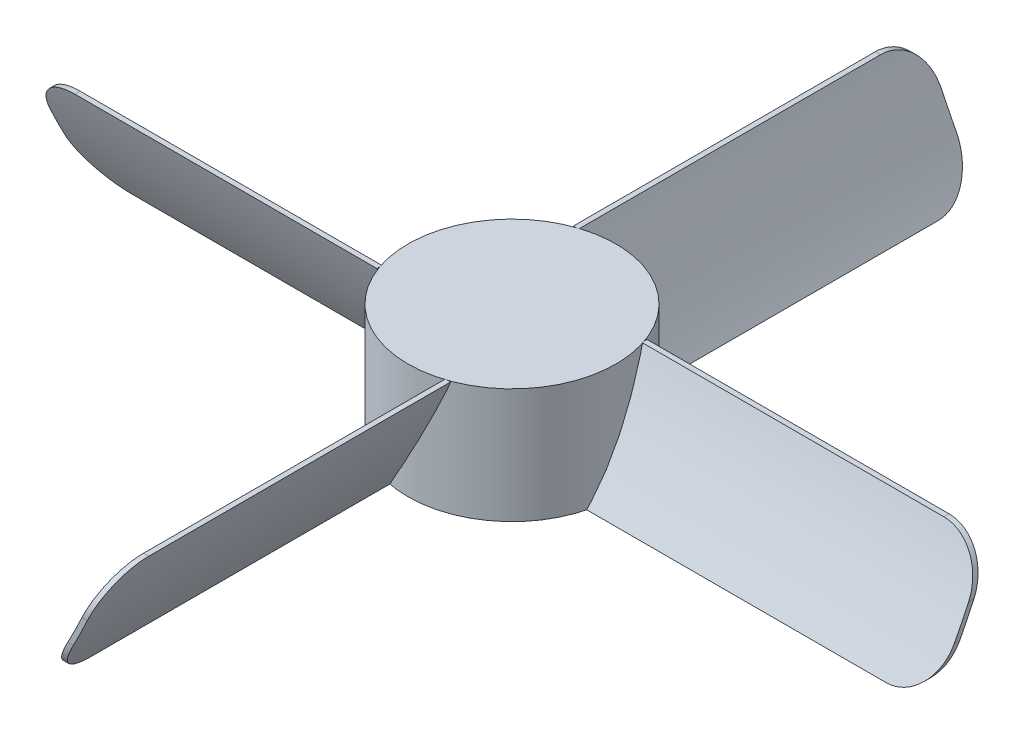
SolidWorks part; units mm, degrees
ref_plane "Front Plane" through (0, 0, 0) normal (0, 0, 1) x (1, 0, 0)
ref_plane "Top Plane" through (0, 0, 0) normal (0, 1, 0) x (1, 0, 0)
ref_plane "Right Plane" through (0, 0, 0) normal (1, 0, 0) x (0, 0, -1)
sketch "Sketch7" plane through (0, 0, 0) normal (0, 0, 1) x (1, 0, 0)
  line L0 (5.9992, 0) -> (-5.9992, 0) construction
  line L1 (10.9077, 20) -> (10, 20)
  line L2 (0, 0) -> (1, 0)
  arc A0 (0, 0) -> (10, 20) centre (-97.3948, 61.1974) ccw
  arc A1 (10.9077, 20) -> (1, 0) centre (-97.3948, 61.1974) cw
  dimension "D3" = 10
extrude "Boss-Extrude2" add sketch "Sketch7" along normal blind 60 contours A0 L1 A1 L2
fillet "Fillet1" radius 7.5 2 edges at (0.5, 0, 60) (10.4539, 20, 60)
sketch "Sketch10" plane through (0, 0, 0) normal (0, 1, 0) x (1, 0, 0)
  line L0 (0, 0) -> (9.0039, 0)
  line L2 (10.9077, 0) -> (10, 0) construction
  line L3 (1, 0) -> (10.9077, 0) construction
  line L4 (4.5019, 0) -> (4.5019, 17.0863)
  circle A0 centre (4.5019, 17.0863) radius 18.0863
  circle A1 centre (4.5019, 17.0863) radius 11.3083
  point P10 (0, 0)
  dimension "D3" = 22.6166
extrude "Boss-Extrude3" add sketch "Sketch10" along normal blind 20 separate body contours A0 A1 | A1 region at (-13.0729, 0, -17.0864) region at (12.2719, 0, -9.3163)
extrude "Cut-Extrude1" cut sketch "Sketch10<3>" along normal blind 10 contours A1
sketch "Sketch10<3>" plane through (0, 0, 0) normal (0, 1, 0) x (1, 0, 0) same geometry as "Sketch10"
pattern_circular "CirPattern1" count 4 over 360 about axis through (4.5019, 20, -17.0863) along (0, -1, 0) of bodies 102
equation "\"insidebladediameter\"=0.0361727"
equation "\"height\"=0.02"
equation "\"bladethickness\"= 0.001"
equation "\"insidebladeradius\"= \"insidebladediameter\" / 2"
equation "\"D1@Sketch7\"=\"bladethickness\""
equation "\"D2@Sketch7\"=\"height\""
equation "\"bladewidth\"= 0.01"
equation "\"bladelength\"=0.06"
equation "\"D1@Boss-Extrude2\"=\"bladelength\""
equation "\"bladetipradius\"=0.0075"
equation "\"D1@Fillet1\"=\"bladetipradius\""
equation "\"D1@Sketch10\"=\"insidebladediameter\""
equation "\"fusedistance\"= \"insidebladeradius\" - 0.001"
equation "\"D2@Sketch10\"=\"fusedistance\""
equation "\"D1@Boss-Extrude3\"=\"height\""
equation "\"numberofblades\"= 4"
equation "\"D1@CirPattern1\"=\"numberofblades\""
equation "\"roddiameter\"=0.0226166"
equation "\"D3@Sketch10\"=\"roddiameter\""
equation "\"roddepth\"=0.01"
equation "\"D1@Cut-Extrude1\"=\"roddepth\""
